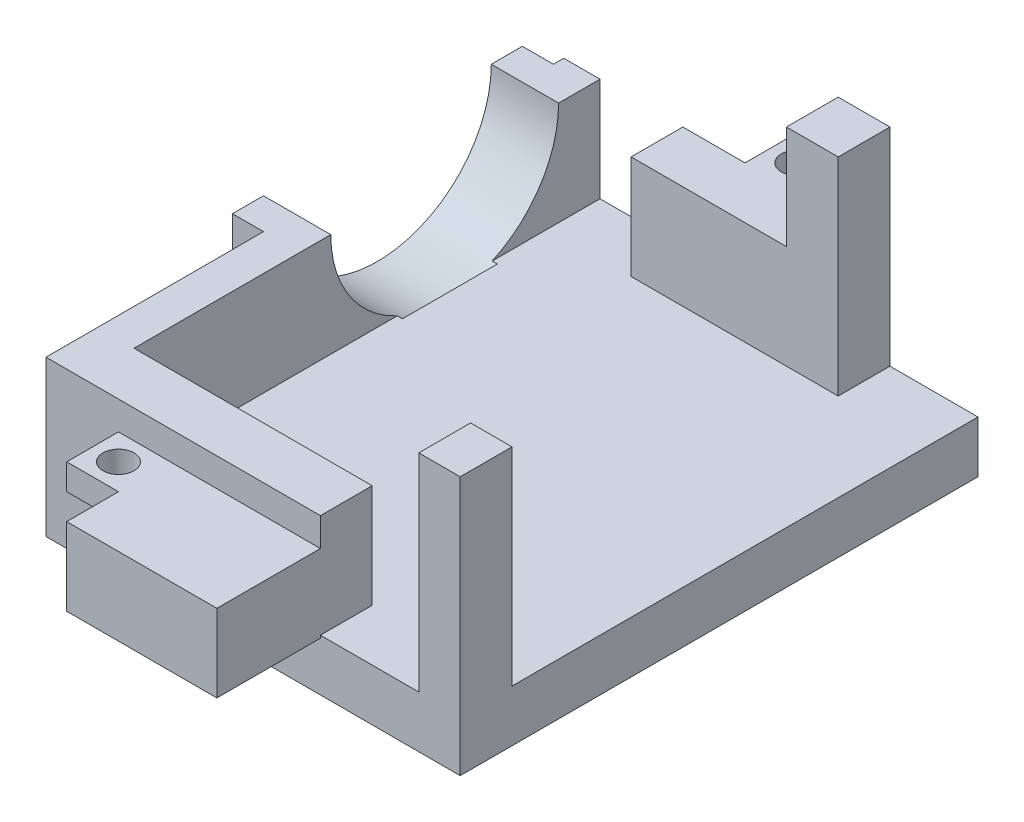
SolidWorks part; units mm, degrees
ref_plane "Front Plane" through (0, 0, 0) normal (0, 0, 1) x (1, 0, 0)
ref_plane "Top Plane" through (0, 0, 0) normal (0, 1, 0) x (1, 0, 0)
ref_plane "Right Plane" through (0, 0, 0) normal (1, 0, 0) x (0, 0, -1)
sketch "Sketch1" plane through (0, 0, 0) normal (0, 1, 0) x (1, 0, 0)
  line L1 (-20, 25) -> (20, 25)
  line L2 (-20, 25) -> (-20, -25)
  line L3 (-20, -25) -> (20, -25)
  line L4 (20, 25) -> (20, -25)
  point P6 (20, 0)
  point P7 (0, 25)
  dimension "D1" = 40
  dimension "D2" = 50
extrude "Boss-Extrude1" add sketch "Sketch1" along normal blind 5
sketch "Sketch3" plane through (0, 5, 0) normal (0, 1, 0) x (1, 0, 0)
  line L0 (20, 25) -> (-20, 25) construction
  line L1 (-8.5, 25) -> (6.5, 25)
  line L2 (-8.5, 25) -> (-8.5, 20)
  line L3 (-8.5, 20) -> (6.5, 20)
  line L4 (6.5, 25) -> (6.5, 20)
  line L5 (20, -25) -> (20, 25) construction
  line L6 (-20, -25) -> (20, -25) construction
  line L7 (-20, 25) -> (-16.5, 25)
  line L10 (-16.5, 25) -> (-16.5, -20)
  line L11 (20, -25) -> (16, -25)
  line L12 (20, -25) -> (20, -20)
  line L13 (20, -20) -> (16, -20)
  line L14 (16, -25) -> (16, -20)
  line L15 (6.5, -25) -> (-20, -25)
  line L16 (6.5, -25) -> (6.5, -20)
  line L17 (6.5, -20) -> (-16.5, -20)
  line L20 (16, 25) -> (16, 20) construction
  line L21 (16, 20) -> (20, 20) construction
  line L22 (-20, 25) -> (-20, -25)
  line L23 (6.5, -20) -> (11.5, -20) construction
  line L24 (11.5, -20) -> (11.5, -25) construction
  line L26 (6.5, 20) -> (11.5, 20)
  line L27 (6.5, 20) -> (6.5, 25)
  line L28 (6.5, 25) -> (11.5, 25)
  line L29 (11.5, 20) -> (11.5, 25)
  line M17 (-20, 25) -> (-20, -25)
  line M18 (-20, -25) -> (20, -25)
  line M19 (20, -25) -> (20, 25)
  line M20 (20, 25) -> (-20, 25)
  dimension "D1" = 8
  dimension "D2" = 15
  dimension "D3" = 3.5
  dimension "D4" = 5
  dimension "D5" = 4
  dimension "D9" = 5
extrude "Boss-Extrude5" add sketch "Sketch3" along normal blind 20 contours L14 L13 M18 M19 | L26 L29 L4 M20 region at (9, 5, -22.5) region at (18, 5, 22.5)
extrude "Boss-Extrude6" add sketch "Sketch3<3>" along normal blind 10 contours L4 L2 L3 M20 | L16 L17 L10 M20 M17 M18 region at (-1, 5, -22.5) region at (-17.0659, 5, -2.5)
sketch "Sketch3<3>" plane through (0, 5, 0) normal (0, 1, 0) x (1, 0, 0) same geometry as "Sketch3"
sketch "Sketch8" plane through (-20, 0, 0) normal (-1, 0, 0) x (0, 0, 1)
  line L0 (-25, 15) -> (25, 15) construction
  line L1 (1, 15) -> (-21, 15)
  arc A0 (-21, 15) -> (1, 15) centre (-10, 15) ccw
  dimension "D1" = 22
  dimension "D2" = 4
extrude "Cut-Extrude3" cut sketch "Sketch8" against normal blind 4
sketch "Sketch10" plane through (-20, 0, 0) normal (-1, 0, 0) x (0, 0, 1)
  line L0 (1, 15) -> (4, 15)
  line L1 (1, 15) -> (25, 15) construction
  line L2 (4, 15) -> (4, 0)
  line L3 (-25, 0) -> (25, 0) construction
  line L4 (4, 0) -> (-24, 0)
  line L5 (-24, 0) -> (-24, 15)
  line L6 (-25, 15) -> (-21, 15) construction
  line L7 (-24, 15) -> (-21, 15)
  arc A0 (-21, 15) -> (1, 15) centre (-10, 15) ccw
  dimension "D2" = 11
  dimension "D1" = 3
extrude "Boss-Extrude9" add sketch "Sketch10" along normal blind 3
sketch "Sketch12" plane through (0, 0, -25) normal (0, 0, -1) x (-1, 0, 0)
  line L0 (-6.5, 15) -> (8.5, 15) construction
  line L1 (-2.5, 15) -> (2.5, 15)
  line L2 (-2.5, 15) -> (-2.5, 10)
  line L3 (-2.5, 10) -> (2.5, 10)
  line L4 (2.5, 15) -> (2.5, 10)
  point P7 (0, 10)
  dimension "D1" = 5
  dimension "D2" = 5
extrude "Boss-Extrude10" add sketch "Sketch12" along normal blind 5
sketch "Sketch13" plane through (0, 10, 0) normal (0, -1, 0) x (1, 0, 0)
  line L0 (-2.5, -30) -> (-2.5, -25) construction
  line L1 (2.5, -30) -> (-2.5, -30) construction
  circle A0 centre (0, -27.5) radius 1.5
  point P5 (-2.5, -27.5)
  point P8 (0, -30)
  dimension "D1" = 3
extrude "Cut-Extrude4" cut sketch "Sketch13" against normal blind 5
sketch "Sketch16" plane through (0, 0, 25) normal (0, 0, 1) x (1, 0, 0)
  line L0 (6.5, 4.75) -> (-8, 4.75)
  line L1 (-8, 4.75) -> (-8, 9.75)
  line L2 (-8, 9.75) -> (-13, 9.75)
  line L3 (-13, 9.75) -> (-13, 12.25)
  line L4 (-13, 12.25) -> (6.5, 12.25)
  line L5 (6.5, 15) -> (6.5, 5) construction
  line L6 (6.5, 12.25) -> (6.5, 4.75)
  line L7 (-8, 9.75) -> (-8, 12.25)
  line L8 (-20, 0) -> (20, 0) construction
  line M12 (6.5, 5) -> (6.5, 15)
  dimension "D1" = 2.5
  dimension "D2" = 5
  dimension "D3" = 7.5
  dimension "D4" = 19.5
  dimension "D5" = 4.75
extrude "Boss-Extrude13" add sketch "Sketch16" along normal blind 5 contours L2 L7 L4 L3 region at (-10.5, 11, 25)
extrude "Boss-Extrude14" add sketch "Sketch16<3>" along normal blind 10 contours L7 L1 L0 L4 M12 region at (-0.75, 8.5, 25)
sketch "Sketch16<3>" plane through (0, 0, 25) normal (0, 0, 1) x (1, 0, 0) same geometry as "Sketch16"
sketch "Sketch17" plane through (0, 9.75, 0) normal (0, -1, 0) x (1, 0, 0)
  line L0 (-13, 30) -> (-13, 25) construction
  line L1 (-8, 30) -> (-13, 30) construction
  circle A0 centre (-10.5, 27.5) radius 1.5
  point P4 (-13, 27.5)
  point P7 (-10.5, 30)
  dimension "D1" = 3
extrude "Cut-Extrude6" cut sketch "Sketch17" against normal blind 2.5
